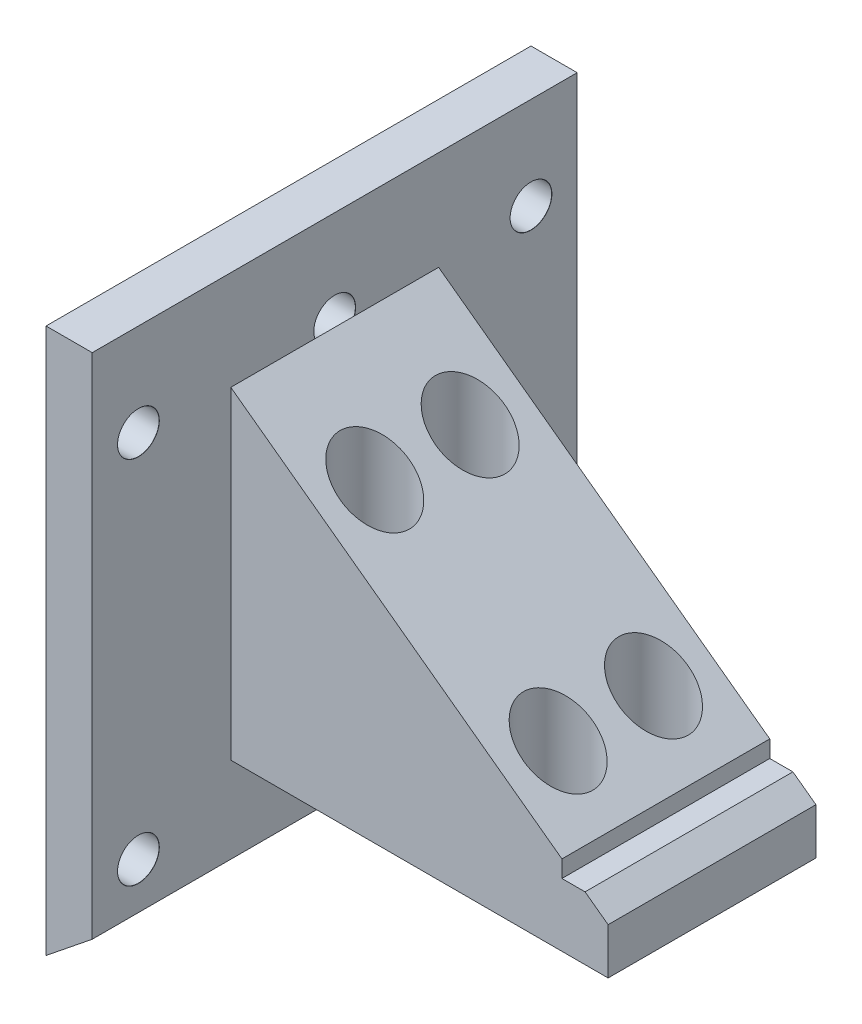
SolidWorks part; units mm, degrees
ref_plane "Front Plane" through (0, 0, 0) normal (0, 0, 1) x (1, 0, 0)
ref_plane "Top Plane" through (0, 0, 0) normal (0, 1, 0) x (1, 0, 0)
ref_plane "Right Plane" through (0, 0, 0) normal (1, 0, 0) x (0, 0, -1)
sketch "Sketch1" plane through (0, 0, 0) normal (0, 0, 1) x (1, 0, 0)
  line L4 (0, 60) -> (10, 60)
  line L5 (10, 60) -> (10, -21.4124)
  line L6 (10, -21.4124) -> (91.7, -21.4124)
  line L7 (91.7, -21.4124) -> (91.7, -31.4124)
  line L8 (91.7, -31.4124) -> (10, -31.4124)
  line L9 (10, -31.4124) -> (10, -60)
  line L10 (10, -60) -> (0, -60)
  line L16 (0, 60) -> (0, -60)
  point P0 (91.7, -13.0648)
  point P2 (0, 0)
  dimension "D3" = 10
  dimension "D4" = 10
  dimension "D9" = 10
  dimension "D10" = 28.5876
  dimension "D11" = 120
  dimension "D12" = 81.7
extrude "Boss-Extrude1" add sketch "Sketch1" along normal blind 22.5 and the other way blind 22.5
sketch "Sketch7" plane through (10, 0, 0) normal (1, 0, 0) x (0, 0, -1)
  line L0 (22.5, 60) -> (-22.5, 60) construction
  point P0 (0, 40)
  dimension "D1" = 20
sketch "Sketch8" plane through (0, 0, -22.5) normal (0, 0, -1) x (-1, 0, 0)
  line L12 (-10, 60) -> (0, 60)
  line L13 (-10, 60) -> (-10, -60)
  line L14 (-10, -60) -> (0, -60)
  line L15 (0, 60) -> (0, -60)
extrude "Boss-Extrude2" add sketch "Sketch8" along normal blind 30
hole_wizard "M8 Clearance Hole2" positions "Sketch17" profile "Sketch10" hole size "M8" standard "ANSI Metric"
sketch "Sketch17" plane through (10, 0, 0) normal (1, 0, 0) x (0, 0, -1)
  line L1 (52.5, -60) -> (-22.5, -60) construction
  line L3 (52.5, 60) -> (52.5, -60) construction
  point P0 (0, 40)
  point P3 (42.5, -40)
  point P12 (42.5, 40)
  dimension "D1" = 20
  dimension "D2" = 10
sketch "Sketch10" plane through (10, 40, 0) normal (0, 1, 0) x (0, 0, -1)
  line L0 (0, 0) -> (0, 25.7039)
  line L1 (0, 25.7039) -> (4.5, 23)
  line L2 (4.5, 23) -> (4.5, 0.025)
  line L3 (4.5, 0.025) -> (4.525, 0)
  line L5 (4.525, 0) -> (0, 0)
  line L6 (-4.5, 0.025) -> (-4.525, 0) construction
  line L10 (0, 25.7039) -> (-4.5, 23) construction
  line L11 (0, -6.35) -> (0, 107.95) construction
  dimension "Hole Dia." = 9
  dimension "Hole Depth" = 23
  dimension "Near C'Sink Dia." = 9.05
  dimension "Near C'Sink Angle" = 90
  dimension "Drill Angle" = 118
sketch "Sketch14" plane through (0, 0, 22.5) normal (0, 0, 1) x (1, 0, 0)
  line L0 (10, 38.5) -> (91.7, -21.4124)
  line L1 (10, -21.4124) -> (10, 60) construction
  line L4 (10, 38.5) -> (10, -21.4124)
  line L5 (10, -21.4124) -> (91.7, -21.4124)
  line M6 (91.7, -21.4124) -> (10, -21.4124)
  line M8 (10, -21.4124) -> (10, 60)
extrude "Boss-Extrude3" add sketch "Sketch14" against normal up to surface (45 mm away) contours L0 M8 M6 region at (37.2333, -1.4416, 22.5) up to face at (50.85, -26.4124, -22.5)
sketch "Sketch2" plane through (0, -31.4124, 0) normal (0, 1, 0) x (1, 0, 0)
  line L1 (91.7, 22.5) -> (91.7, -22.5) construction
  circle A0 centre (68.7, 10.325) radius 2.38
  circle A1 centre (68.7, -10.325) radius 2.38
  circle A2 centre (29, 10.325) radius 2.38
  circle A3 centre (29, -10.325) radius 2.38
  dimension "D1" = 4.76
  dimension "D2" = 39.7
  dimension "D3" = 20.65
  dimension "D4" = 10.325
  dimension "D5" = 23
extrude "Cut-Extrude1" cut sketch "Sketch2" along normal blind 60
mirror "Mirror2" about plane through (0, 0, 0) normal (0, 0, 1) of "M8 Clearance Hole2", "Boss-Extrude2"
chamfer "Chamfer4" distance 10 angle 51.19 1 edges at (10, -60, 0) first distance on face at (10, -40, 37.975)
sketch "Sketch18" plane through (0, 60, 0) normal (0, 1, 0) x (1, 0, 0)
  circle A0 centre (29, 10.325) radius 7.5
  circle A1 centre (29, -10.325) radius 7.5
  circle A2 centre (68.7, 10.325) radius 7.5
  circle A3 centre (68.7, -10.325) radius 7.5
  dimension "D1" = 15
  dimension "D2" = 15
  dimension "D3" = 15
  dimension "D4" = 15
extrude "Cut-Extrude4" cut sketch "Sketch18" against normal blind 85
sketch "Sketch19" plane through (91.7, 0, 0) normal (1, 0, 0) x (0, 0, -1)
  line L1 (-27.8409, -17.7532) -> (33.9173, -17.7532)
  line L2 (-27.8409, -17.7532) -> (-27.8409, 7.7676)
  line L3 (-27.8409, 7.7676) -> (33.9173, 7.7676)
  line L4 (33.9173, -17.7532) -> (33.9173, 7.7676)
extrude "Cut-Extrude5" cut sketch "Sketch19" against normal blind 10
